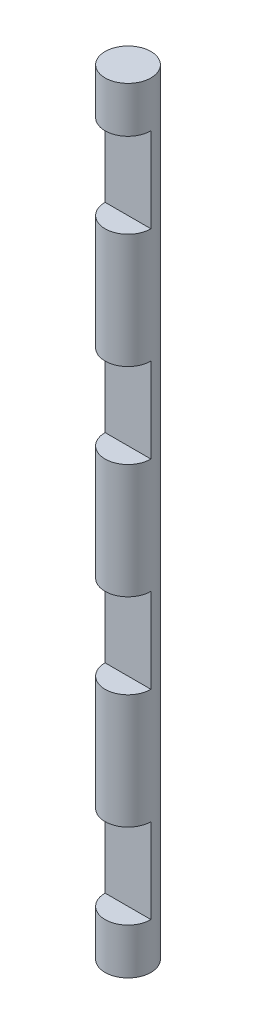
SolidWorks part; units mm, degrees
material "ABS"
ref_plane "Front Plane" through (0, 0, 0) normal (0, 0, 1) x (1, 0, 0)
ref_plane "Top Plane" through (0, 0, 0) normal (0, 1, 0) x (1, 0, 0)
ref_plane "Right Plane" through (0, 0, 0) normal (1, 0, 0) x (0, 0, -1)
sketch "Sketch1" plane through (0, 0, 0) normal (0, 1, 0) x (1, 0, 0)
  circle A0 centre (0, 0) radius 13
  dimension "D1" = 26
extrude "Boss-Extrude1" add sketch "Sketch1" along normal blind 1
ref_plane "Plane1" through (0, 1, 0) normal (0, 1, 0) x (1, 0, 0)
ref_plane "Plane2" through (0, 4.7, 0) normal (0, 1, 0) x (1, 0, 0)
ref_plane "Plane3" through (0, 9.7, 0) normal (0, 1, 0) x (1, 0, 0)
ref_plane "Plane4" through (0, 13.4, 0) normal (0, 1, 0) x (1, 0, 0)
ref_plane "Plane5" through (0, 18.4, 0) normal (0, 1, 0) x (1, 0, 0)
ref_plane "Plane6" through (0, 22.1, 0) normal (0, 1, 0) x (1, 0, 0)
ref_plane "Plane7" through (0, 27.1, 0) normal (0, 1, 0) x (1, 0, 0)
ref_plane "Plane8" through (0, 30.8, 0) normal (0, 1, 0) x (1, 0, 0)
sketch "Sketch16" plane through (0, 30.8, 0) normal (0, 1, 0) x (1, 0, 0)
  circle A0 centre (0, 0) radius 13
  circle A1 centre (0, 0) radius 13 construction
  dimension "D1" = 0
extrude "Boss-Extrude3" add sketch "Sketch16" along normal blind 1 separate body
sketch "Sketch18" plane through (0, 4.7, 0) normal (0, 1, 0) x (1, 0, 0)
  line L1 (-11, -11) -> (11, -11)
  line L2 (-11, -11) -> (-11, 11)
  line L3 (-11, 11) -> (11, 11)
  line L4 (11, -11) -> (11, 11)
  dimension "D1" = 22
  dimension "D2" = 22
  dimension "D3" = 11
  dimension "D4" = 11
sketch "Sketch19" plane through (0, 1, 0) normal (0, 1, 0) x (1, 0, 0)
  circle A0 centre (0, 11) radius 1
  point P13 (0, 0)
  dimension "D1" = 2
  dimension "D2" = 11
extrude "Boss-Extrude4" add sketch "Sketch19" along normal up to surface (29.8 mm away) up to face at (0, 30.8, 13)
extrude "Cut-Extrude6" cut sketch "Sketch18" against normal blind 3.7
sketch "Sketch21" plane through (0, 13.4, 0) normal (0, 1, 0) x (1, 0, 0)
  line L1 (-11, -11) -> (11, -11)
  line L2 (-11, -11) -> (-11, 11)
  line L3 (-11, 11) -> (11, 11)
  line L4 (11, -11) -> (11, 11)
  dimension "D1" = 22
  dimension "D2" = 22
  dimension "D3" = 11
  dimension "D4" = 11
extrude "Cut-Extrude7" cut sketch "Sketch21" against normal blind 3.7
sketch "Sketch22" plane through (0, 22.1, 0) normal (0, 1, 0) x (1, 0, 0)
  line L5 (-11, -11) -> (11, -11)
  line L6 (-11, -11) -> (-11, 11)
  line L7 (-11, 11) -> (11, 11)
  line L8 (11, -11) -> (11, 11)
  dimension "D1" = 11
  dimension "D2" = 11
  dimension "D3" = 22
  dimension "D4" = 22
extrude "Cut-Extrude8" cut sketch "Sketch22" against normal blind 3.7
sketch "Sketch23" plane through (0, 30.8, 0) normal (0, 1, 0) x (1, 0, 0)
  line L1 (-11, -11) -> (11, -11)
  line L2 (-11, -11) -> (-11, 11)
  line L3 (-11, 11) -> (11, 11)
  line L4 (11, -11) -> (11, 11)
  dimension "D1" = 22
  dimension "D2" = 22
  dimension "D3" = 11
  dimension "D4" = 11
extrude "Cut-Extrude9" cut sketch "Sketch23" against normal blind 3.7
sketch "Sketch24" plane through (0, 31.8, 0) normal (0, 1, 0) x (1, 0, 0)
  circle A0 centre (0, 0) radius 19.9218
extrude "Cut-Extrude10" cut sketch "Sketch24" against normal blind 1
sketch "Sketch25" plane through (0, 1, 0) normal (0, 1, 0) x (1, 0, 0)
  circle A0 centre (0, 0) radius 36.1829
extrude "Cut-Extrude11" cut sketch "Sketch25" against normal blind 1
sketch "Sketch26" plane through (0, 30.8, 0) normal (0, 1, 0) x (1, 0, 0)
  circle A0 centre (0, 11) radius 1
  arc A2 (1, 11) -> (-1, 11) centre (0, 11) ccw construction
  arc M1 (1, 11) -> (-1, 11) centre (0, 11) ccw
  dimension "D1" = 0
  dimension "D2" = 2
extrude "Boss-Extrude5" add sketch "Sketch26" along normal blind 2 contours M1 | A0 region at (0, 30.8, -11)
sketch "Sketch27" plane through (0, 1, 0) normal (0, -1, 0) x (1, 0, 0)
  circle A0 centre (0, -11) radius 1
extrude "Boss-Extrude6" add sketch "Sketch27" along normal blind 2
